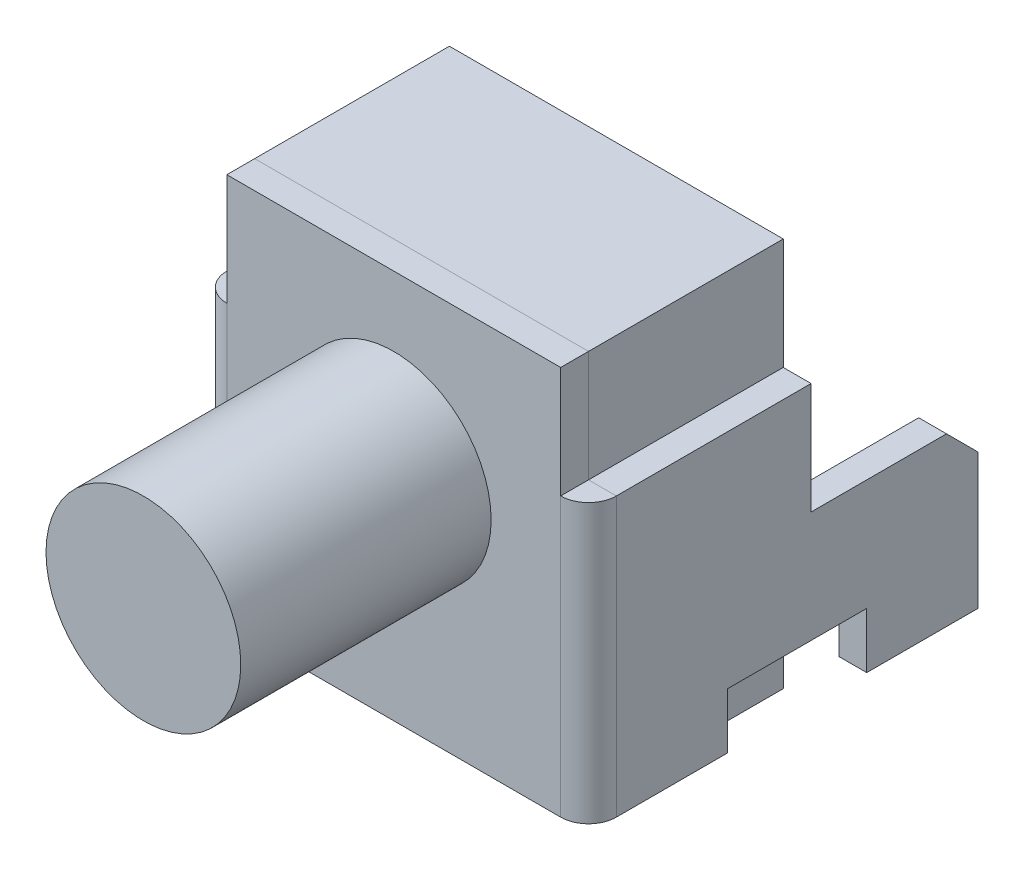
SolidWorks part; units mm, degrees
ref_plane "Front" through (0, 0, 0) normal (0, 0, 1) x (1, 0, 0)
ref_plane "Top" through (0, 0, 0) normal (0, 1, 0) x (1, 0, 0)
ref_plane "Right" through (0, 0, 0) normal (1, 0, 0) x (0, 0, -1)
sketch "Эскиз1" plane through (0, 0, 0) normal (1, 0, 0) x (0, 0, -1)
  line L0 (0, 0) -> (0, 7)
  line L1 (0, 7) -> (3.5, 7)
  line L2 (3.5, 7) -> (3.5, 3)
  line L3 (3.5, 3) -> (5.9343, 3)
  line L4 (5.9343, 3) -> (6.5, 2.4343)
  line L5 (6.5, 2.4343) -> (6.5, 0)
  line L6 (6.5, 0) -> (4.5, 0)
  line L7 (4.5, 0) -> (4.5, 1)
  line L8 (4.5, 1) -> (2, 1)
  line L9 (2, 1) -> (2, 0)
  line L10 (2, 0) -> (0, 0)
  line L11 (0, 5) -> (3.5, 5)
  line L12 (3.5, 3) -> (3.5, 0)
  line L13 (3.5, 0) -> (2, 0)
  dimension "D1" = 3.5
  dimension "D2" = 7
  dimension "D3" = 45
  dimension "D4" = 3
  dimension "D5" = 1
  dimension "D6" = 2
  dimension "D7" = 6.5
  dimension "D8" = 0.8
  dimension "D9" = 2
extrude "Бобышка-Вытянуть1" add sketch "Эскиз1" along normal blind 0.5 contours L11 L0 L10 L9 L8 L7 L6 L5 L4 L3 L2 | L3 L12 L8 L7 L6 L5 L4 region at (0, 2.6875, -1.6563) region at (0, 1.6008, -5.1008)
extrude "Бобышка-Вытянуть2" add sketch "Эскиз1<3>" against normal blind 6 separate body contours L13 L12 L8 L9 | L12 L2 L11 L0 L10 L9 L8 | L0 L11 L2 L1 region at (0, 2.6875, -1.6563) region at (0, 6, -1.75) region at (0, 0.5, -2.75)
sketch "Эскиз1<3>" plane through (0, 0, 0) normal (1, 0, 0) x (0, 0, -1) same geometry as "Эскиз1"
extrude "Бобышка-Вытянуть3" add sketch "Эскиз1<4>" against normal blind 0.5 from surface contours L3 L12 L8 L7 L6 L5 L4 | L12 L2 L11 L0 L10 L9 L8 region at (0, 2.6875, -1.6563) region at (0, 1.6008, -5.1008) starting at face at (-6, 3.5, -1.75)
sketch "Эскиз1<4>" plane through (0, 0, 0) normal (1, 0, 0) x (0, 0, -1) same geometry as "Эскиз1"
sketch "Эскиз2" plane through (0, 0, 0) normal (0, 0, 1) x (1, 0, 0)
  line L1 (0, 7) -> (-6, 7) construction
  line L2 (0, 7) -> (0, 1) construction
  line L3 (0, 1) -> (-6, 1) construction
  line L4 (-6, 7) -> (-6, 1) construction
  line L5 (-3, 1) -> (-3, 7) construction
  line L6 (0, 4) -> (-6, 4) construction
  circle A0 centre (-3, 4) radius 1.75
  point P236 (-3, 4)
  dimension "D1" = 3.5
extrude "Бобышка-Вытянуть4" add sketch "Эскиз2" along normal blind 5 contours A0 region at (-3, 4, 0)
sketch "Эскиз3" plane through (0, 0, 0) normal (0, 0, 1) x (1, 0, 0)
  line L4 (0, 0) -> (0, 7)
  line L5 (0, 7) -> (-6, 7)
  line L6 (-6, 7) -> (-6, 0)
  line L7 (-6, 0) -> (0, 0)
  line L8 (0, 0) -> (0, 7)
  line L9 (0, 7) -> (-6, 7)
  line L10 (-6, 7) -> (-6, 0)
  line L11 (-6, 0) -> (0, 0)
  circle A0 centre (-3, 4) radius 1.75 construction
  circle A1 centre (-3, 4) radius 1.75
  dimension "D1" = 0
extrude "Бобышка-Вытянуть5" add sketch "Эскиз3" along normal blind 0.5 separate body
sketch "Эскиз4" plane through (0, 5, 0) normal (0, 1, 0) x (1, 0, 0)
  line L0 (-6.5, 0) -> (-6, -0.5)
sketch "Эскиз5" plane through (0, 0, 0) normal (0, 0, 1) x (1, 0, 0)
  line L4 (-6, 0) -> (-6, 5)
  line L5 (-6, 5) -> (-6.5, 5)
  line L6 (-6.5, 5) -> (-6.5, 0)
  line L7 (-6.5, 0) -> (-6, 0)
  line L8 (-6, 0) -> (-6, 5)
  line L9 (-6, 5) -> (-6.5, 5)
  line L10 (-6.5, 5) -> (-6.5, 0)
  line L11 (-6.5, 0) -> (-6, 0)
  dimension "D1" = 0
revolve "Повернуть1" add sketch "Эскиз5" angle 90 about L8
sketch "Эскиз6" plane through (0, 0, 0) normal (0, 0, 1) x (1, 0, 0)
  line L4 (0, 5) -> (0, 0)
  line L5 (0, 0) -> (0.5, 0)
  line L6 (0.5, 0) -> (0.5, 5)
  line L7 (0.5, 5) -> (0, 5)
  line L8 (0, 5) -> (0, 0)
  line L9 (0, 0) -> (0.5, 0)
  line L10 (0.5, 0) -> (0.5, 5)
  line L11 (0.5, 5) -> (0, 5)
  dimension "D1" = 0
revolve "Повернуть2" add sketch "Эскиз6" angle 90 about L8
